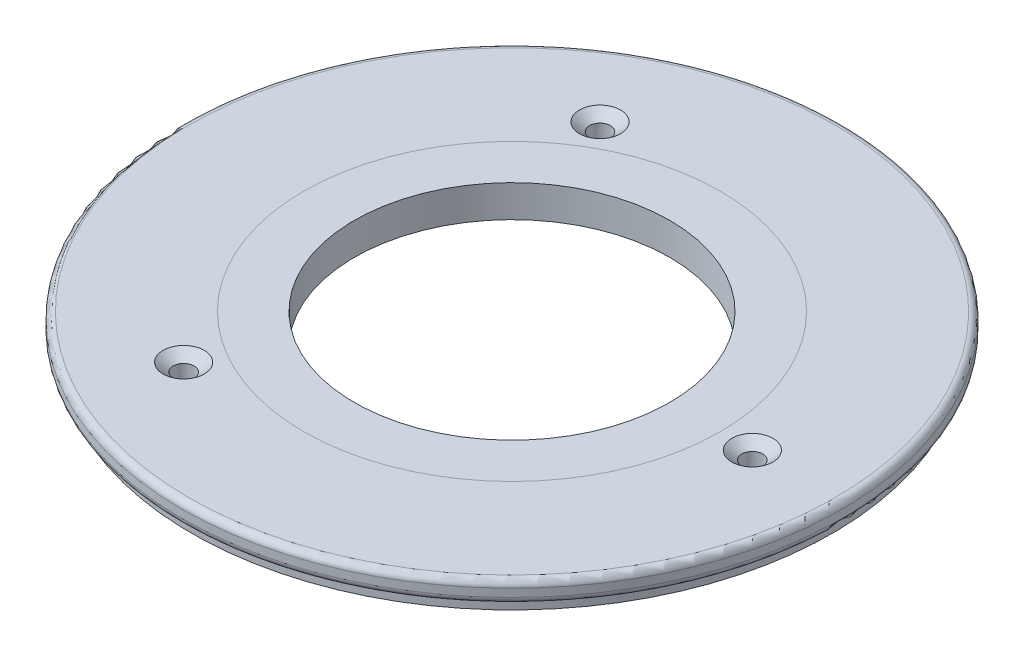
SolidWorks part; units mm, degrees
material "Delrin 2700 NC010, Low Viscosity Acetal Copolymer (SS)"
ref_plane "Front Plane" through (0, 0, 0) normal (0, 0, 1) x (1, 0, 0)
ref_plane "Top Plane" through (0, 0, 0) normal (0, 1, 0) x (1, 0, 0)
ref_plane "Right Plane" through (0, 0, 0) normal (1, 0, 0) x (0, 0, -1)
sketch "Sketch1" plane through (0, 0, 0) normal (0, 1, 0) x (1, 0, 0)
  circle A0 centre (0, 0) radius 78.359
  circle A1 centre (0, 0) radius 37.5031
  dimension "D1" = 75.0062
  dimension "D2" = 156.718
extrude "Boss-Extrude1" add sketch "Sketch1" along normal blind 7.62
hole_wizard "CSK for #10 Flat Head Machine Screw (100)1" positions "Sketch4" profile "Sketch5" countersink size "#10" standard "ANSI Inch" end condition through all
sketch "Sketch4" plane through (0, 7.62, 0) normal (0, 1, 0) x (1, 0, 0)
  line L0 (-65.4508, 0) -> (95.8403, 0) construction
  point P0 (57.15, 0)
  dimension "D1" = 57.15
sketch "Sketch5" plane through (57.15, 7.62, 0) normal (1, 0, 0) x (0, 0, 1)
  line L0 (0, 0) -> (0, 7.62)
  line L1 (0, 7.62) -> (2.4892, 7.62)
  line L2 (2.4892, 7.62) -> (2.4892, 2.0141)
  line L3 (2.4892, 2.0141) -> (4.8895, 0)
  line L5 (4.8895, 0) -> (0, 0)
  line L6 (-2.4892, 2.0141) -> (-4.8895, 0) construction
  line L11 (0, -6.35) -> (0, 107.95) construction
  dimension "Thru Hole Dia." = 4.9784
  dimension "Thru Hole Depth" = 7.62
  dimension "Near C'Sink Dia." = 9.779
  dimension "Near C'Sink Angle" = 100
pattern_circular "CirPattern1" count 4 every 120 about axis through (0, 7.62, 0) along (0, 1, 0) of "CSK for #10 Flat Head Machine Screw (100)1"
sketch "Sketch6" plane through (0, 0, 0) normal (0, -1, 0) x (1, 0, 0)
  circle A0 centre (0, 0) radius 76.1746
  circle A1 centre (0, 0) radius 78.359
  dimension "D2" = 156.718
  dimension "D1" = 152.3492
extrude "Cut-Extrude1" cut sketch "Sketch6" against normal blind 2.54
fillet "Fillet1" radius 1.5875 2 edges at (0, 2.54, -78.359) (0, 7.62, 78.359)
sketch "Sketch7" plane through (0, 7.62, 0) normal (0, 1, 0) x (1, 0, 0)
  circle A0 centre (0, 0) radius 49.53
  dimension "D1" = 99.06
split line "Split Line1"
equation "\"ID\"= 2.953in"
equation "\"D1@Sketch1\"=\"ID\""
equation "\"OD\"= 6.17in"
equation "\"h\"= 0.3"
equation "\"D1@Boss-Extrude1\"=\"h\""
equation "\"HoleDist\"= 2.25"
equation "\"D1@Sketch4\"=\"HoleDist\""
equation "\"D2@Sketch1\"=\"OD\""
equation "\"CouplerDia\"= 5.998"
equation "\"D1@Sketch6\"=\"CouplerDia\""
equation "\"D2@Sketch6\"=\"OD\""
